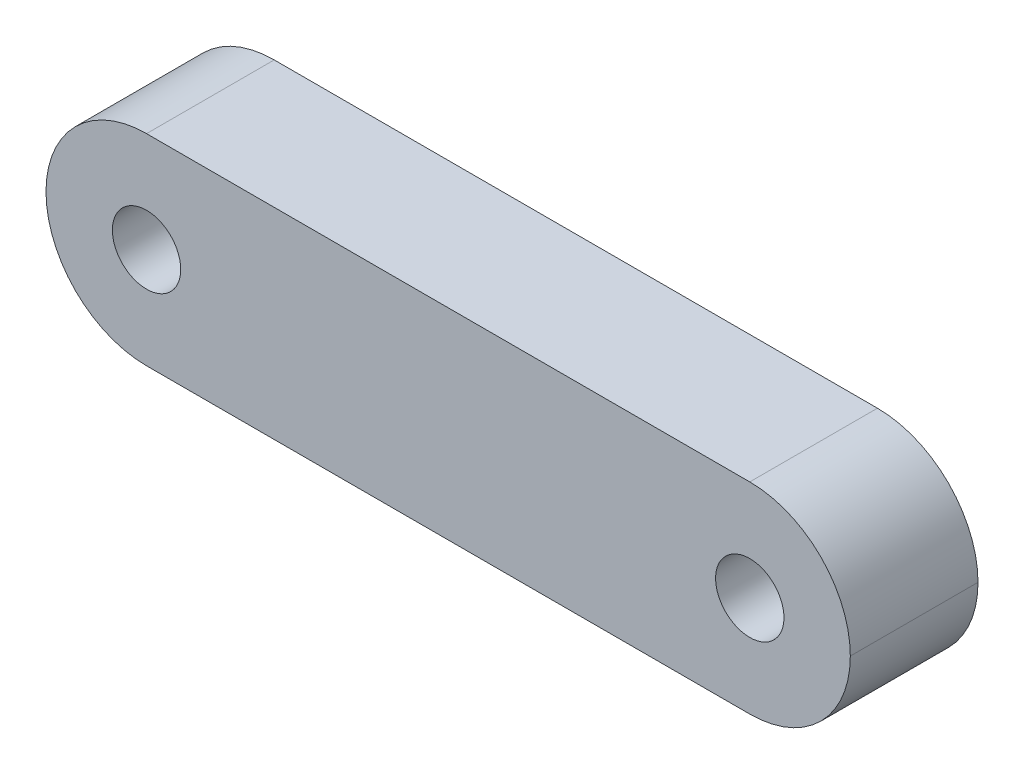
SolidWorks part; units mm, degrees
ref_plane "Front Plane" through (0, 0, 0) normal (0, 0, 1) x (1, 0, 0)
ref_plane "Top Plane" through (0, 0, 0) normal (0, 1, 0) x (1, 0, 0)
ref_plane "Right Plane" through (0, 0, 0) normal (1, 0, 0) x (0, 0, -1)
sketch "Sketch1" plane through (0, 0, 0) normal (0, 0, 1) x (1, 0, 0)
  line L1 (0, 0) -> (40, 0)
  line L2 (0, 0) -> (0, 10)
  line L3 (0, 10) -> (40, 10)
  line L4 (40, 0) -> (40, 10)
  circle A1 centre (35, 5) radius 1.7
  circle A2 centre (5, 5) radius 1.7
  dimension "D3" = 5
  dimension "D4" = 3.4
  dimension "D5" = 5
  dimension "D6" = 3.4
  dimension "D1" = 10
  dimension "D2" = 40
extrude "Boss-Extrude1" add sketch "Sketch1" along normal blind 6.35 contours L1 L4 L3 L2 A2 A1 | A2 region at (20, 5, 0)
fillet "Fillet1" radius 5 4 edges at (0, 10, 3.175) (0, 0, 3.175) (40, 10, 3.175) (40, 0, 3.175)
